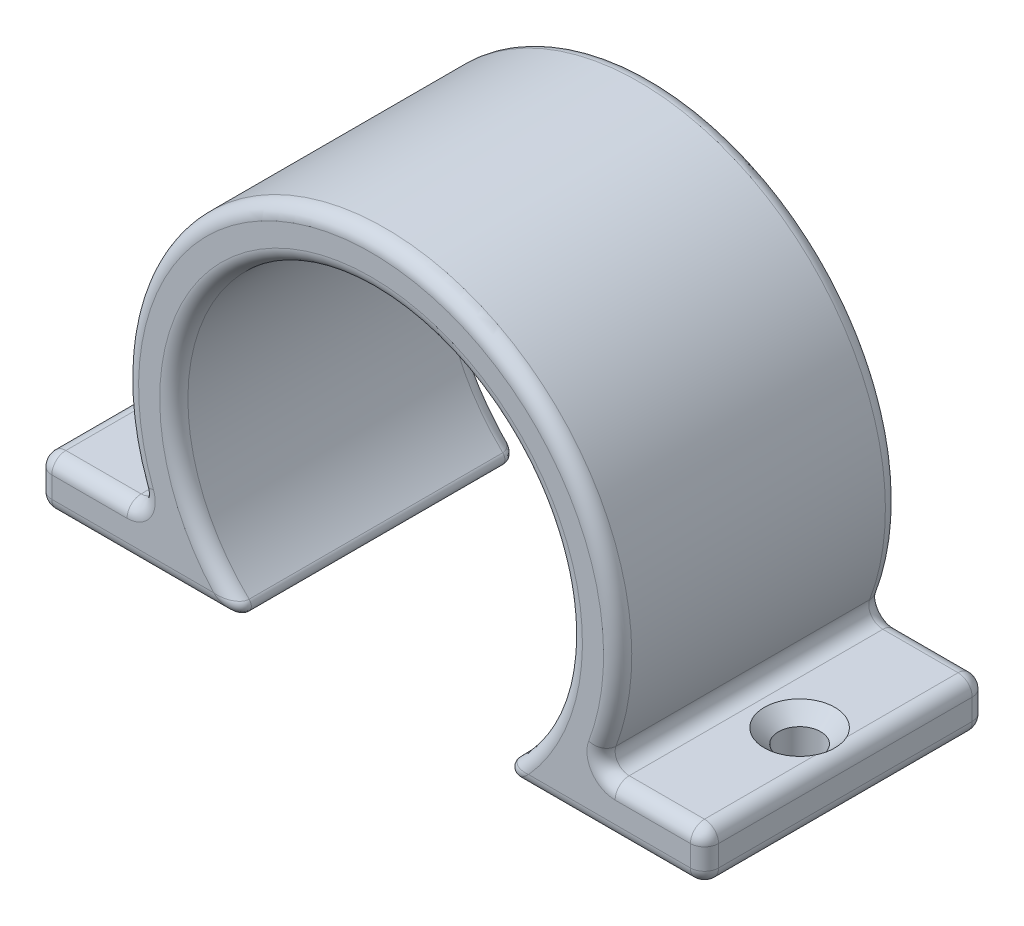
SolidWorks part; units mm, degrees
material "ABS"
ref_plane "Front Plane" through (0, 0, 0) normal (0, 0, 1) x (1, 0, 0)
ref_plane "Top Plane" through (0, 0, 0) normal (0, 1, 0) x (1, 0, 0)
ref_plane "Right Plane" through (0, 0, 0) normal (1, 0, 0) x (0, 0, -1)
sketch "Sketch2" plane through (0, 0, 0) normal (0, 0, 1) x (1, 0, 0)
  line L0 (-23.6603, -11) -> (-8.6603, -11)
  line L1 (8.6603, -11) -> (23.6603, -11)
  line L2 (15.8114, -7.5) -> (23.6603, -7.5)
  line L3 (-23.6603, -7.5) -> (-15.8114, -7.5)
  line L4 (-23.6603, -7.5) -> (-23.6603, -11)
  line L5 (23.6603, -7.5) -> (23.6603, -11)
  arc A0 (8.6603, -11) -> (-8.6603, -11) centre (0, 0) ccw
  arc A1 (15.8114, -7.5) -> (-15.8114, -7.5) centre (0, 0) ccw
  point P6 (0, -14)
  dimension "D1" = 28
  dimension "D2" = 3
  dimension "D3" = 15
  dimension "D4" = 3.5
extrude "Boss-Extrude1" add sketch "Sketch2" along normal mid plane 20
fillet "Fillet1" radius 0.5 2 edges at (8.6603, -11, 0) (-8.6603, -11, 0)
sketch "Sketch3" plane through (0, -7.5, 0) normal (0, 1, 0) x (1, 0, 0)
  line L0 (-23.6603, -10) -> (-23.6603, 10) construction
  line L1 (-15.8114, -10) -> (-23.6603, -10) construction
  line L2 (0, -11) -> (0, 11) construction
  circle A0 centre (-20.4103, 0) radius 1.5
  circle A1 centre (20.4103, 0) radius 1.5
  dimension "D1" = 3
  dimension "D2" = 3.25
  dimension "D3" = 10
extrude "Cut-Extrude1" cut sketch "Sketch3" against normal through all
fillet "Fillet2" radius 1 26 edges at (23.6603, -11, 0) (23.6603, -7.5, 0) (-23.6603, -7.5, 0) (-23.6603, -11, 0) (23.6603, -9.25, -10) (19.7358, -7.5, -10) (0, 17.5, -10) (-19.7358, -7.5, -10) (-23.6603, -9.25, -10) (-16.8301, -11, -10) (-9.5358, -10.6857, -10) (0, 14, -10) (9.5358, -10.6857, -10) (16.8301, -11, -10) (-9.5358, -10.6857, 10) (-16.8301, -11, 10) (-23.6603, -9.25, 10) (-19.7358, -7.5, 10) (0, 17.5, 10) (19.7358, -7.5, 10) (23.6603, -9.25, 10) (16.8301, -11, 10) (9.5358, -10.6857, 10) (0, 14, 10) (-15.8114, -7.5, 0) (15.8114, -7.5, 0)
chamfer "Chamfer1" distance 1 angle 45 2 edges at (-20.4103, -7.5, 1.5) (20.4103, -7.5, -1.5)
